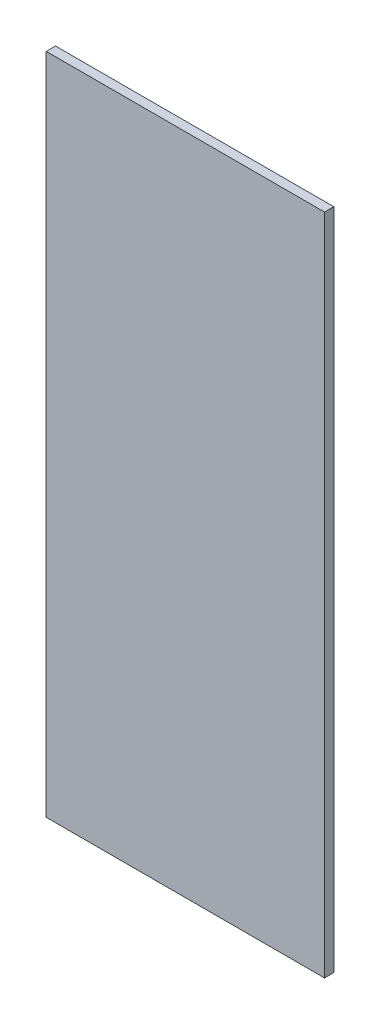
SolidWorks part; units mm, degrees
ref_plane "Front Plane" through (0, 0, 0) normal (0, 0, 1) x (1, 0, 0)
ref_plane "Top Plane" through (0, 0, 0) normal (0, 1, 0) x (1, 0, 0)
ref_plane "Right Plane" through (0, 0, 0) normal (1, 0, 0) x (0, 0, -1)
sketch "Sketch1" plane through (0, 0, 0) normal (0, 0, 1) x (1, 0, 0)
  line L1 (-30, -71.5) -> (30, -71.5)
  line L2 (-30, -71.5) -> (-30, 71.5)
  line L3 (-30, 71.5) -> (30, 71.5)
  line L4 (30, -71.5) -> (30, 71.5)
  line L5 (-30, -71.5) -> (30, 71.5) construction
  line L6 (-30, 71.5) -> (30, -71.5) construction
  point P0 (0, 0)
  dimension "D1" = 60
  dimension "D2" = 143
base flange "Base-Flange1" sketch "Sketch1" thickness 2 reverse thickness direction no parameters "D1"=1
sketch "Bend-Lines1" [suppressed] plane through (0, 0, 0) normal (0, 1, 0) x (1, 0, 0)
sketch "Bounding-Box1" [suppressed] plane through (0, 0, 0) normal (0, 1, 0) x (1, 0, 0)
sheet metal parameters "Sheet-Metal1" thickness 2 parameters "D1"=1
flat pattern "Flat-Pattern1" [suppressed]
sketch "Bend-Lines2" plane through (0, 0, 0) normal (0, 1, 0) x (1, 0, 0)
sketch3d "Bounding-Box2" [suppressed]
  line L0 (-30, 71.5, 0) -> (-30, -71.5, 0) construction
  line L1 (30, 71.5, 0) -> (30, -71.5, 0) construction
  line L2 (-30, 71.5, 0) -> (30, 71.5, 0) construction
  line L3 (-30, -71.5, 0) -> (30, -71.5, 0) construction
